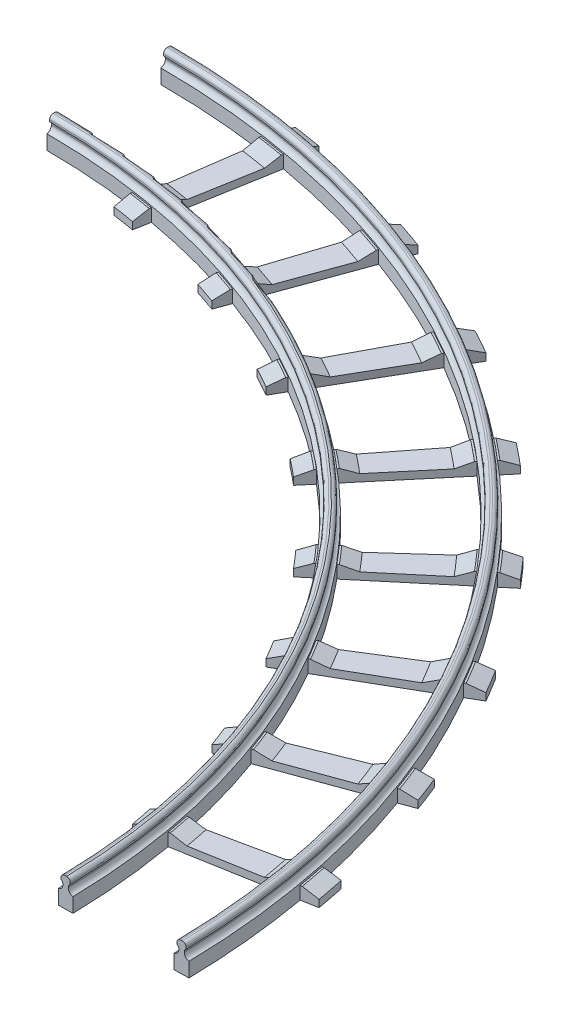
SolidWorks part; units mm, degrees
note: The reader was unsure of these and kept them because the rebuilt part matched: shared geometry of "草图1<7>", "草图2<3>", "草图5<2>".
other "标注1"
sketch "草图3" plane through (-22.25, 4, -10) normal (-0.231, 0.6469, -0.7268) x (-0.9696, -0.2151, 0.1167)
other "标注2"
sketch "草图4" plane through (22.25, 8, -30) normal (0.0083, 0.0567, -0.9984) x (-0.9991, 0.0415, -0.0059)
ref_plane "前视基准面" through (0, 0, 0) normal (0, 0, 1) x (1, 0, 0)
ref_plane "上视基准面" through (0, 0, 0) normal (0, 1, 0) x (1, 0, 0)
ref_plane "右视基准面" through (0, 0, 0) normal (1, 0, 0) x (0, 0, -1)
other "Configuration Table"
sketch "草图1" plane through (0, 0, 0) normal (0, 1, 0) x (1, 0, 0)
  line L0 (-13.75, 14.5) -> (-13.75, -14.5)
  line L13 (-17.75, -14.5) -> (17.75, -14.5)
  line L21 (-17.75, -14.5) -> (-17.75, 14.5)
  line L22 (-17.75, 14.5) -> (17.75, 14.5)
  line L23 (17.75, -14.5) -> (17.75, 14.5)
  line L24 (-17.75, -14.5) -> (17.75, 14.5) construction
  line L25 (-17.75, 14.5) -> (17.75, -14.5) construction
  line L27 (13.75, 14.5) -> (13.75, -14.5)
  line L29 (-13.75, 0) -> (13.75, 0) construction
  line L32 (-22.25, 14.5) -> (22.25, 14.5)
  line L33 (-22.25, 14.5) -> (-22.25, 6.5)
  line L34 (-22.25, 6.5) -> (22.25, 6.5)
  line L35 (22.25, 14.5) -> (22.25, 6.5)
  point P0 (0, 0)
  point P15 (0, 6.5)
  dimension "D3" = 27.5
  dimension "D4" = 8
  dimension "D1" = 35.5
  dimension "D2" = 29
  dimension "D5" = 44.5
extrude "凸台-拉伸1" add sketch "草图1" along normal blind 4 contours L34 L21 L13 L0 | L34 L27 L13 L23 | L27 L34 L23 L22 | L21 L34 L0 L22
extrude "凸台-拉伸2" add sketch "草图1<7>" along normal blind 3.5 contours L34 L35 L32 L33
sketch "草图1<7>" plane through (0, 0, 0) normal (0, 1, 0) x (1, 0, 0) same geometry as "草图1"
sketch "草图2" plane through (0, 0, -14.5) normal (0, 0, -1) x (-1, 0, 0)
  line L0 (18.25, 3.5) -> (22.25, 2)
  line L1 (22.25, 3.5) -> (18.25, 3.5)
  line L2 (22.25, 3.5) -> (22.25, 2)
  line L3 (22.25, 2) -> (18.25, 2) construction
  line L4 (18.25, 3.5) -> (18.25, 2) construction
  line L5 (-22.25, 2) -> (-18.25, 3.5)
  line L6 (-22.25, 3.5) -> (-18.25, 3.5)
  line L7 (-22.25, 3.5) -> (-22.25, 2)
  line L8 (-22.25, 2) -> (-18.25, 2) construction
  line L9 (-18.25, 3.5) -> (-18.25, 2) construction
  line L10 (13.75, 3.5) -> (-13.75, 3.5) construction
  line L11 (-13.25, 3.5) -> (-9.25, 3.5)
  line L12 (-13.25, 3.5) -> (-13.25, 2) construction
  line L13 (-13.25, 2) -> (-9.25, 2) construction
  line L14 (-9.25, 3.5) -> (-9.25, 2)
  line L15 (-13.75, 3.5) -> (-13.25, 3.5) construction
  line L16 (13.25, 3.5) -> (9.25, 3.5)
  line L17 (13.25, 3.5) -> (13.25, 2) construction
  line L18 (13.25, 2) -> (9.25, 2) construction
  line L19 (9.25, 3.5) -> (9.25, 2)
  line L20 (13.25, 3.5) -> (13.75, 3.5) construction
  line L21 (17.75, 3.5) -> (18.25, 3.5) construction
  line L22 (-13.25, 3.5) -> (-9.25, 2)
  line L23 (9.25, 2) -> (13.25, 3.5)
  line L24 (-9.25, 2) -> (9.25, 2)
  line L25 (-9.25, 3.5) -> (9.25, 3.5)
  line L26 (-15.75, 4) -> (-15.75, 6.5) construction
  line L27 (14.5, 8) -> (17, 8)
  line L28 (14.5, 8) -> (14.5, 6.5)
  line L29 (14.5, 6.5) -> (17, 6.5)
  line L30 (17, 8) -> (17, 6.5)
  line L31 (-17, 8) -> (-14.5, 8)
  line L32 (-17, 8) -> (-17, 6.5)
  line L33 (-17, 6.5) -> (-14.5, 6.5)
  line L34 (-14.5, 8) -> (-14.5, 6.5)
  line L35 (-13.75, 4) -> (-17.75, 4) construction
  line L36 (15.75, 6.5) -> (15.75, 4) construction
  line L37 (17.75, 4) -> (13.75, 4) construction
  line L38 (15, 6.5) -> (15, 4)
  line L39 (16.5, 6.5) -> (16.5, 4)
  line L40 (16.5, 4) -> (15.75, 4)
  line L41 (15.75, 4) -> (15, 4)
  line L42 (-16.5, 6.5) -> (-16.5, 4)
  line L43 (-16.5, 4) -> (-15.75, 4)
  line L44 (-15.75, 4) -> (-15, 4)
  line L45 (-15, 4) -> (-15, 6.5)
  line M9 (22.25, 3.5) -> (17.75, 3.5)
  line M11 (17.75, 4) -> (13.75, 4)
  line M13 (13.75, 3.5) -> (-13.75, 3.5)
  line M15 (-13.75, 4) -> (-17.75, 4)
  line M17 (-17.75, 3.5) -> (-22.25, 3.5)
  line M18 (-22.25, 3.5) -> (-22.25, 0)
  line M20 (22.25, 0) -> (22.25, 3.5)
  dimension "D1" = 4
  dimension "D2" = 1.5
  dimension "D3" = 2.5
  dimension "D4" = 1.5
  dimension "D5" = 2.5
  dimension "D6" = 1.5
extrude "切除-拉伸1" cut sketch "草图2" against normal through all contours L14 L24 L19 M13 | L19 L23 M13 | L22 L14 M13 | L5 M18 M17 | L0 M9 M20
extrude "凸台-拉伸4" add sketch "草图2<3>" against normal through all contours L34 L31 L32 L33 | L45 L33 L42 M15 | L30 L27 L28 L29 | L39 L29 L38 M11
sketch "草图2<3>" plane through (0, 0, -14.5) normal (0, 0, -1) x (-1, 0, 0) same geometry as "草图2"
fillet "圆角1" radius 1 4 edges at (-16.5, 6.5, 0) (-15, 6.5, 0) (15, 6.5, 0) (16.5, 6.5, 0)
fillet "圆角2" radius 1.5 4 edges at (16.5, 4, 0) (15, 4, 0) (-15, 4, 0) (-16.5, 4, 0)
fillet "圆角3" radius 1 4 edges at (-17, 8, 0) (14.5, 8, 0) (17, 8, 0) (-14.5, 8, 0)
sketch "草图5" plane through (0, 0, -14.5) normal (0, 0, -1) x (-1, 0, 0)
  line L26 (17, 6.5) -> (17, 7)
  line L27 (16, 8) -> (15.5, 8)
  line L28 (14.5, 7) -> (14.5, 6.5)
  line L29 (15, 5.634) -> (15, 5.479)
  line L30 (13.75, 4) -> (13.75, 3.5)
  line L31 (13.75, 3.5) -> (13.25, 3.5)
  line L32 (13.25, 3.5) -> (9.25, 2)
  line L33 (9.25, 2) -> (-9.25, 2)
  line L34 (-9.25, 2) -> (-13.25, 3.5)
  line L35 (-13.25, 3.5) -> (-13.75, 3.5)
  line L36 (-13.75, 3.5) -> (-13.75, 4)
  line L37 (-15, 5.479) -> (-15, 5.634)
  line L38 (-14.5, 6.5) -> (-14.5, 7)
  line L39 (-15.5, 8) -> (-16, 8)
  line L40 (-17, 7) -> (-17, 6.5)
  line L41 (-16.5, 5.634) -> (-16.5, 5.479)
  line L42 (-17.75, 4) -> (-17.75, 3.5)
  line L43 (-17.75, 3.5) -> (-18.25, 3.5)
  line L44 (-18.25, 3.5) -> (-22.25, 2)
  line L45 (-22.25, 2) -> (-22.25, 0)
  line L46 (-22.25, 0) -> (22.25, 0)
  line L47 (22.25, 0) -> (22.25, 2)
  line L48 (22.25, 2) -> (18.25, 3.5)
  line L49 (18.25, 3.5) -> (17.75, 3.5)
  line L50 (17.75, 3.5) -> (17.75, 4)
  line L51 (16.5, 5.479) -> (16.5, 5.634)
  line L52 (17, 6.5) -> (17, 7)
  line L53 (16, 8) -> (15.5, 8)
  line L54 (14.5, 7) -> (14.5, 6.5)
  line L55 (15, 5.634) -> (15, 5.479)
  line L56 (13.75, 4) -> (13.75, 3.5)
  line L57 (13.75, 3.5) -> (13.25, 3.5)
  line L58 (13.25, 3.5) -> (9.25, 2)
  line L59 (9.25, 2) -> (-9.25, 2)
  line L60 (-9.25, 2) -> (-13.25, 3.5)
  line L61 (-13.25, 3.5) -> (-13.75, 3.5)
  line L62 (-13.75, 3.5) -> (-13.75, 4)
  line L63 (-15, 5.479) -> (-15, 5.634)
  line L64 (-14.5, 6.5) -> (-14.5, 7)
  line L65 (-15.5, 8) -> (-16, 8)
  line L66 (-17, 7) -> (-17, 6.5)
  line L67 (-16.5, 5.634) -> (-16.5, 5.479)
  line L68 (-17.75, 4) -> (-17.75, 3.5)
  line L69 (-17.75, 3.5) -> (-18.25, 3.5)
  line L70 (-18.25, 3.5) -> (-22.25, 2)
  line L71 (-22.25, 2) -> (-22.25, 0)
  line L72 (-22.25, 0) -> (22.25, 0)
  line L73 (22.25, 0) -> (22.25, 2)
  line L74 (22.25, 2) -> (18.25, 3.5)
  line L75 (18.25, 3.5) -> (17.75, 3.5)
  line L76 (17.75, 3.5) -> (17.75, 4)
  line L77 (16.5, 5.479) -> (16.5, 5.634)
  arc A12 (17, 7) -> (16, 8) centre (16, 7) ccw
  arc A13 (15.5, 8) -> (14.5, 7) centre (15.5, 7) ccw
  arc A14 (15, 5.634) -> (14.5, 6.5) centre (14, 5.634) ccw
  arc A15 (13.75, 4) -> (15, 5.479) centre (13.5, 5.479) ccw
  arc A16 (-15, 5.479) -> (-13.75, 4) centre (-13.5, 5.479) ccw
  arc A17 (-14.5, 6.5) -> (-15, 5.634) centre (-14, 5.634) ccw
  arc A18 (-14.5, 7) -> (-15.5, 8) centre (-15.5, 7) ccw
  arc A19 (-16, 8) -> (-17, 7) centre (-16, 7) ccw
  arc A20 (-16.5, 5.634) -> (-17, 6.5) centre (-17.5, 5.634) ccw
  arc A21 (-17.75, 4) -> (-16.5, 5.479) centre (-18, 5.479) ccw
  arc A22 (16.5, 5.479) -> (17.75, 4) centre (18, 5.479) ccw
  arc A23 (17, 6.5) -> (16.5, 5.634) centre (17.5, 5.634) ccw
  arc A24 (17, 7) -> (16, 8) centre (16, 7) ccw
  arc A25 (15.5, 8) -> (14.5, 7) centre (15.5, 7) ccw
  arc A26 (15, 5.634) -> (14.5, 6.5) centre (14, 5.634) ccw
  arc A27 (13.75, 4) -> (15, 5.479) centre (13.5, 5.479) ccw
  arc A28 (-15, 5.479) -> (-13.75, 4) centre (-13.5, 5.479) ccw
  arc A29 (-14.5, 6.5) -> (-15, 5.634) centre (-14, 5.634) ccw
  arc A30 (-14.5, 7) -> (-15.5, 8) centre (-15.5, 7) ccw
  arc A31 (-16, 8) -> (-17, 7) centre (-16, 7) ccw
  arc A32 (-16.5, 5.634) -> (-17, 6.5) centre (-17.5, 5.634) ccw
  arc A33 (-17.75, 4) -> (-16.5, 5.479) centre (-18, 5.479) ccw
  arc A34 (16.5, 5.479) -> (17.75, 4) centre (18, 5.479) ccw
  arc A35 (17, 6.5) -> (16.5, 5.634) centre (17.5, 5.634) ccw
  dimension "D1" = 0
sketch "草图7" plane through (0, 0, -14.5) normal (0, 0, -1) x (-1, 0, 0)
  line L0 (-17.75, 3.5) -> (-17.75, 0)
  line L1 (-13.75, 3.5) -> (-13.75, 0)
  line L2 (13.75, 3.5) -> (13.75, 0)
  line L3 (17.75, 3.5) -> (17.75, 0)
  line L4 (13.75, 0) -> (17.75, 0)
  line L26 (17, 6.5) -> (17, 7)
  line L27 (16, 8) -> (15.5, 8)
  line L28 (14.5, 7) -> (14.5, 6.5)
  line L29 (15, 5.634) -> (15, 5.479)
  line L30 (13.75, 4) -> (13.75, 3.5)
  line L31 (13.75, 3.5) -> (13.25, 3.5)
  line L32 (13.25, 3.5) -> (9.25, 2)
  line L33 (9.25, 2) -> (-9.25, 2)
  line L34 (-9.25, 2) -> (-13.25, 3.5)
  line L35 (-13.25, 3.5) -> (-13.75, 3.5)
  line L36 (-13.75, 3.5) -> (-13.75, 4)
  line L37 (-15, 5.479) -> (-15, 5.634)
  line L38 (-14.5, 6.5) -> (-14.5, 7)
  line L39 (-15.5, 8) -> (-16, 8)
  line L40 (-17, 7) -> (-17, 6.5)
  line L41 (-16.5, 5.634) -> (-16.5, 5.479)
  line L42 (-17.75, 4) -> (-17.75, 3.5)
  line L43 (-17.75, 3.5) -> (-18.25, 3.5)
  line L44 (-18.25, 3.5) -> (-22.25, 2)
  line L45 (-22.25, 2) -> (-22.25, 0)
  line L46 (-22.25, 0) -> (22.25, 0)
  line L47 (22.25, 0) -> (22.25, 2)
  line L48 (22.25, 2) -> (18.25, 3.5)
  line L49 (18.25, 3.5) -> (17.75, 3.5)
  line L50 (17.75, 3.5) -> (17.75, 4)
  line L51 (16.5, 5.479) -> (16.5, 5.634)
  line L52 (17, 6.5) -> (17, 7)
  line L53 (16, 8) -> (15.5, 8)
  line L54 (14.5, 7) -> (14.5, 6.5)
  line L55 (15, 5.634) -> (15, 5.479)
  line L56 (13.75, 4) -> (13.75, 3.5)
  line L62 (-13.75, 3.5) -> (-13.75, 4)
  line L63 (-15, 5.479) -> (-15, 5.634)
  line L64 (-14.5, 6.5) -> (-14.5, 7)
  line L65 (-15.5, 8) -> (-16, 8)
  line L66 (-17, 7) -> (-17, 6.5)
  line L67 (-16.5, 5.634) -> (-16.5, 5.479)
  line L68 (-17.75, 4) -> (-17.75, 3.5)
  line L72 (-17.75, 0) -> (-13.75, 0)
  line L76 (17.75, 3.5) -> (17.75, 4)
  line L77 (16.5, 5.479) -> (16.5, 5.634)
  arc A12 (17, 7) -> (16, 8) centre (16, 7) ccw
  arc A13 (15.5, 8) -> (14.5, 7) centre (15.5, 7) ccw
  arc A14 (15, 5.634) -> (14.5, 6.5) centre (14, 5.634) ccw
  arc A15 (13.75, 4) -> (15, 5.479) centre (13.5, 5.479) ccw
  arc A16 (-15, 5.479) -> (-13.75, 4) centre (-13.5, 5.479) ccw
  arc A17 (-14.5, 6.5) -> (-15, 5.634) centre (-14, 5.634) ccw
  arc A18 (-14.5, 7) -> (-15.5, 8) centre (-15.5, 7) ccw
  arc A19 (-16, 8) -> (-17, 7) centre (-16, 7) ccw
  arc A20 (-16.5, 5.634) -> (-17, 6.5) centre (-17.5, 5.634) ccw
  arc A21 (-17.75, 4) -> (-16.5, 5.479) centre (-18, 5.479) ccw
  arc A22 (16.5, 5.479) -> (17.75, 4) centre (18, 5.479) ccw
  arc A23 (17, 6.5) -> (16.5, 5.634) centre (17.5, 5.634) ccw
  arc A24 (17, 7) -> (16, 8) centre (16, 7) ccw
  arc A25 (15.5, 8) -> (14.5, 7) centre (15.5, 7) ccw
  arc A26 (15, 5.634) -> (14.5, 6.5) centre (14, 5.634) ccw
  arc A27 (13.75, 4) -> (15, 5.479) centre (13.5, 5.479) ccw
  arc A28 (-15, 5.479) -> (-13.75, 4) centre (-13.5, 5.479) ccw
  arc A29 (-14.5, 6.5) -> (-15, 5.634) centre (-14, 5.634) ccw
  arc A30 (-14.5, 7) -> (-15.5, 8) centre (-15.5, 7) ccw
  arc A31 (-16, 8) -> (-17, 7) centre (-16, 7) ccw
  arc A32 (-16.5, 5.634) -> (-17, 6.5) centre (-17.5, 5.634) ccw
  arc A33 (-17.75, 4) -> (-16.5, 5.479) centre (-18, 5.479) ccw
  arc A34 (16.5, 5.479) -> (17.75, 4) centre (18, 5.479) ccw
  arc A35 (17, 6.5) -> (16.5, 5.634) centre (17.5, 5.634) ccw
  dimension "D1" = 0
sketch "草图6" plane through (0, 0, -14.5) normal (0, 0, -1) x (-1, 0, 0)
  line L0 (0, 0) -> (200, 0) construction
  line L1 (200, 10) -> (200, -10)
  dimension "D1" = 200
  dimension "D2" = 20
revolve "旋转2" add sketch "草图7" angle 92 about L1
extrude "切除-拉伸5" cut sketch "草图5<2>" against normal through all
sketch "草图5<2>" plane through (0, 0, -14.5) normal (0, 0, -1) x (-1, 0, 0) same geometry as "草图5"
revolve "旋转1" add sketch "草图5" angle 2 about L1
pattern_circular "阵列(圆周)1" count 10 every 10 about axis through (-200, 0, -14.5) along (0, 1, 0) of "旋转1"
sketch "草图8" plane through (0, 0, -14.5) normal (0, 0, 1) x (1, 0, 0)
  line L78 (-22.25, 2) -> (-22.25, 0)
  line L79 (-22.25, 0) -> (22.25, 0)
  line L80 (22.25, 0) -> (22.25, 2)
  line L81 (22.25, 2) -> (18.25, 3.5)
  line L82 (18.25, 3.5) -> (17.75, 3.5)
  line L83 (17.75, 3.5) -> (17.75, 4)
  line L84 (16.5, 5.479) -> (16.5, 5.634)
  line L85 (17, 6.5) -> (17, 7)
  line L86 (16, 8) -> (15.5, 8)
  line L87 (14.5, 7) -> (14.5, 6.5)
  line L88 (15, 5.634) -> (15, 5.479)
  line L89 (13.75, 4) -> (13.75, 3.5)
  line L90 (13.75, 3.5) -> (13.25, 3.5)
  line L91 (13.25, 3.5) -> (9.25, 2)
  line L92 (9.25, 2) -> (-9.25, 2)
  line L93 (-9.25, 2) -> (-13.25, 3.5)
  line L94 (-13.25, 3.5) -> (-13.75, 3.5)
  line L95 (-13.75, 3.5) -> (-13.75, 4)
  line L96 (-15, 5.479) -> (-15, 5.634)
  line L97 (-14.5, 6.5) -> (-14.5, 7)
  line L98 (-15.5, 8) -> (-16, 8)
  line L99 (-17, 7) -> (-17, 6.5)
  line L100 (-16.5, 5.634) -> (-16.5, 5.479)
  line L101 (-17.75, 4) -> (-17.75, 3.5)
  line L102 (-17.75, 3.5) -> (-18.25, 3.5)
  line L103 (-18.25, 3.5) -> (-22.25, 2)
  line L104 (-22.25, 2) -> (-22.25, 0)
  line L105 (-22.25, 0) -> (22.25, 0)
  line L106 (22.25, 0) -> (22.25, 2)
  line L107 (22.25, 2) -> (18.25, 3.5)
  line L108 (18.25, 3.5) -> (17.75, 3.5)
  line L109 (17.75, 3.5) -> (17.75, 4)
  line L110 (16.5, 5.479) -> (16.5, 5.634)
  line L111 (17, 6.5) -> (17, 7)
  line L112 (16, 8) -> (15.5, 8)
  line L113 (14.5, 7) -> (14.5, 6.5)
  line L114 (15, 5.634) -> (15, 5.479)
  line L115 (13.75, 4) -> (13.75, 3.5)
  line L116 (13.75, 3.5) -> (13.25, 3.5)
  line L117 (13.25, 3.5) -> (9.25, 2)
  line L118 (9.25, 2) -> (-9.25, 2)
  line L119 (-9.25, 2) -> (-13.25, 3.5)
  line L120 (-13.25, 3.5) -> (-13.75, 3.5)
  line L121 (-13.75, 3.5) -> (-13.75, 4)
  line L122 (-15, 5.479) -> (-15, 5.634)
  line L123 (-14.5, 6.5) -> (-14.5, 7)
  line L124 (-15.5, 8) -> (-16, 8)
  line L125 (-17, 7) -> (-17, 6.5)
  line L126 (-16.5, 5.634) -> (-16.5, 5.479)
  line L127 (-17.75, 4) -> (-17.75, 3.5)
  line L128 (-17.75, 3.5) -> (-18.25, 3.5)
  line L129 (-18.25, 3.5) -> (-22.25, 2)
  arc A36 (16.5, 5.479) -> (17.75, 4) centre (18, 5.479) ccw
  arc A37 (17, 6.5) -> (16.5, 5.634) centre (17.5, 5.634) ccw
  arc A38 (17, 7) -> (16, 8) centre (16, 7) ccw
  arc A39 (15.5, 8) -> (14.5, 7) centre (15.5, 7) ccw
  arc A40 (15, 5.634) -> (14.5, 6.5) centre (14, 5.634) ccw
  arc A41 (13.75, 4) -> (15, 5.479) centre (13.5, 5.479) ccw
  arc A42 (-15, 5.479) -> (-13.75, 4) centre (-13.5, 5.479) ccw
  arc A43 (-14.5, 6.5) -> (-15, 5.634) centre (-14, 5.634) ccw
  arc A44 (-14.5, 7) -> (-15.5, 8) centre (-15.5, 7) ccw
  arc A45 (-16, 8) -> (-17, 7) centre (-16, 7) ccw
  arc A46 (-16.5, 5.634) -> (-17, 6.5) centre (-17.5, 5.634) ccw
  arc A47 (-17.75, 4) -> (-16.5, 5.479) centre (-18, 5.479) ccw
  arc A48 (16.5, 5.479) -> (17.75, 4) centre (18, 5.479) ccw
  arc A49 (17, 6.5) -> (16.5, 5.634) centre (17.5, 5.634) ccw
  arc A50 (17, 7) -> (16, 8) centre (16, 7) ccw
  arc A51 (15.5, 8) -> (14.5, 7) centre (15.5, 7) ccw
  arc A52 (15, 5.634) -> (14.5, 6.5) centre (14, 5.634) ccw
  arc A53 (13.75, 4) -> (15, 5.479) centre (13.5, 5.479) ccw
  arc A54 (-15, 5.479) -> (-13.75, 4) centre (-13.5, 5.479) ccw
  arc A55 (-14.5, 6.5) -> (-15, 5.634) centre (-14, 5.634) ccw
  arc A56 (-14.5, 7) -> (-15.5, 8) centre (-15.5, 7) ccw
  arc A57 (-16, 8) -> (-17, 7) centre (-16, 7) ccw
  arc A58 (-16.5, 5.634) -> (-17, 6.5) centre (-17.5, 5.634) ccw
  arc A59 (-17.75, 4) -> (-16.5, 5.479) centre (-18, 5.479) ccw
  dimension "D1" = 0
revolve "切除-旋转1" cut sketch "草图8" angle 1 about L1
sketch "草图9" plane through (-199.2507, 0, 6.958) normal (-0.9994, 0, 0.0349) x (0.0349, 0, 0.9994)
  line L8 (-243.7211, 0) -> (-199.2211, 0)
  line L16 (-243.7211, 0) -> (-199.2211, 0)
  line L24 (-203.7211, 3.5) -> (-203.7211, 4)
  line L26 (-203.7211, 3.5) -> (-203.7211, 4)
  line L28 (-204.9711, 5.479) -> (-204.9711, 5.634)
  line L30 (-204.9711, 5.479) -> (-204.9711, 5.634)
  line L32 (-204.4711, 6.5) -> (-204.4711, 7)
  line L34 (-204.4711, 6.5) -> (-204.4711, 7)
  line L94 (-205.4711, 8) -> (-205.9711, 8)
  line L98 (-205.4711, 8) -> (-205.9711, 8)
  line L102 (-206.9711, 7) -> (-206.9711, 6.5)
  line L106 (-206.9711, 7) -> (-206.9711, 6.5)
  line L110 (-206.4711, 5.634) -> (-206.4711, 5.479)
  line L113 (-206.4711, 5.634) -> (-206.4711, 5.479)
  line L115 (-207.7211, 4) -> (-207.7211, 3.5)
  line L117 (-207.7211, 4) -> (-207.7211, 3.5)
  line L119 (-235.2211, 3.5) -> (-235.2211, 4)
  line L121 (-235.2211, 3.5) -> (-235.2211, 4)
  line L123 (-236.4711, 5.479) -> (-236.4711, 5.634)
  line L124 (-236.4711, 5.479) -> (-236.4711, 5.634)
  line L125 (-235.9711, 6.5) -> (-235.9711, 7)
  line L126 (-235.9711, 6.5) -> (-235.9711, 7)
  line L127 (-236.9711, 8) -> (-237.4711, 8)
  line L128 (-236.9711, 8) -> (-237.4711, 8)
  line L129 (-238.4711, 7) -> (-238.4711, 6.5)
  line L130 (-238.4711, 7) -> (-238.4711, 6.5)
  line L131 (-237.9711, 5.634) -> (-237.9711, 5.479)
  line L132 (-237.9711, 5.634) -> (-237.9711, 5.479)
  line L133 (-239.2211, 4) -> (-239.2211, 3.5)
  line L134 (-239.2211, 4) -> (-239.2211, 3.5)
  line L135 (-199.2211, 0) -> (-199.2211, 2)
  line L136 (-199.2211, 0) -> (-199.2211, 2)
  line L137 (-199.2211, 2) -> (-203.2211, 3.5)
  line L138 (-199.2211, 2) -> (-203.2211, 3.5)
  line L139 (-203.2211, 3.5) -> (-203.7211, 3.5)
  line L140 (-203.2211, 3.5) -> (-203.7211, 3.5)
  line L141 (-207.7211, 3.5) -> (-208.2211, 3.5)
  line L142 (-207.7211, 3.5) -> (-208.2211, 3.5)
  line L143 (-208.2211, 3.5) -> (-212.2211, 2)
  line L144 (-208.2211, 3.5) -> (-212.2211, 2)
  line L145 (-212.2211, 2) -> (-230.7211, 2)
  line L146 (-212.2211, 2) -> (-230.7211, 2)
  line L147 (-230.7211, 2) -> (-234.7211, 3.5)
  line L148 (-230.7211, 2) -> (-234.7211, 3.5)
  line L149 (-234.7211, 3.5) -> (-235.2211, 3.5)
  line L150 (-234.7211, 3.5) -> (-235.2211, 3.5)
  line L151 (-239.2211, 3.5) -> (-239.7211, 3.5)
  line L152 (-239.2211, 3.5) -> (-239.7211, 3.5)
  line L153 (-239.7211, 3.5) -> (-243.7211, 2)
  line L154 (-239.7211, 3.5) -> (-243.7211, 2)
  line L155 (-243.7211, 2) -> (-243.7211, 0)
  line L156 (-243.7211, 2) -> (-243.7211, 0)
  arc A6 (-204.9711, 5.479) -> (-203.7211, 4) centre (-203.4711, 5.479) ccw
  arc A14 (-204.9711, 5.479) -> (-203.7211, 4) centre (-203.4711, 5.479) ccw
  arc A19 (-204.4711, 6.5) -> (-204.9711, 5.634) centre (-203.9711, 5.634) ccw
  arc A21 (-204.4711, 6.5) -> (-204.9711, 5.634) centre (-203.9711, 5.634) ccw
  arc A23 (-204.4711, 7) -> (-205.4711, 8) centre (-205.4711, 7) ccw
  arc A38 (-204.4711, 7) -> (-205.4711, 8) centre (-205.4711, 7) ccw
  arc A54 (-205.9711, 8) -> (-206.9711, 7) centre (-205.9711, 7) ccw
  arc A55 (-205.9711, 8) -> (-206.9711, 7) centre (-205.9711, 7) ccw
  arc A56 (-206.4711, 5.634) -> (-206.9711, 6.5) centre (-207.4711, 5.634) ccw
  arc A57 (-206.4711, 5.634) -> (-206.9711, 6.5) centre (-207.4711, 5.634) ccw
  arc A58 (-207.7211, 4) -> (-206.4711, 5.479) centre (-207.9711, 5.479) ccw
  arc A59 (-207.7211, 4) -> (-206.4711, 5.479) centre (-207.9711, 5.479) ccw
  arc A60 (-236.4711, 5.479) -> (-235.2211, 4) centre (-234.9711, 5.479) ccw
  arc A61 (-236.4711, 5.479) -> (-235.2211, 4) centre (-234.9711, 5.479) ccw
  arc A62 (-235.9711, 6.5) -> (-236.4711, 5.634) centre (-235.4711, 5.634) ccw
  arc A63 (-235.9711, 6.5) -> (-236.4711, 5.634) centre (-235.4711, 5.634) ccw
  arc A64 (-235.9711, 7) -> (-236.9711, 8) centre (-236.9711, 7) ccw
  arc A65 (-235.9711, 7) -> (-236.9711, 8) centre (-236.9711, 7) ccw
  arc A66 (-237.4711, 8) -> (-238.4711, 7) centre (-237.4711, 7) ccw
  arc A67 (-237.4711, 8) -> (-238.4711, 7) centre (-237.4711, 7) ccw
  arc A68 (-237.9711, 5.634) -> (-238.4711, 6.5) centre (-238.9711, 5.634) ccw
  arc A69 (-237.9711, 5.634) -> (-238.4711, 6.5) centre (-238.9711, 5.634) ccw
  arc A70 (-239.2211, 4) -> (-237.9711, 5.479) centre (-239.4711, 5.479) ccw
  arc A71 (-239.2211, 4) -> (-237.9711, 5.479) centre (-239.4711, 5.479) ccw
  dimension "D1" = 0
revolve "切除-旋转2" cut sketch "草图9" angle 1 about L1
sketch "草图10" plane through (-0.3139, 0, -17.9855) normal (0.0175, 0, 0.9998) x (0.9998, 0, -0.0175)
  line L0 (-17.4665, 3.5) -> (-17.4665, 0)
  line L1 (-13.4665, 3.5) -> (-13.4665, 0)
  line L2 (14.0335, 3.5) -> (14.0335, 0)
  line L3 (18.0335, 3.5) -> (18.0335, 0)
  line L4 (-13.4665, 0) -> (14.0335, 0)
  line L5 (18.0335, 0) -> (22.5335, 0)
  line L26 (-17.9665, 3.5) -> (-21.9665, 2)
  line L27 (-21.9665, 2) -> (-21.9665, 0)
  line L28 (-21.9665, 0) -> (22.5335, 0)
  line L29 (22.5335, 0) -> (22.5335, 2)
  line L30 (22.5335, 2) -> (18.5335, 3.5)
  line L31 (18.5335, 3.5) -> (18.0335, 3.5)
  line L32 (18.0335, 3.5) -> (18.0335, 4)
  line L33 (16.7835, 5.479) -> (16.7835, 5.634)
  line L34 (17.2835, 6.5) -> (17.2835, 7)
  line L35 (16.2835, 8) -> (15.7835, 8)
  line L36 (14.7835, 7) -> (14.7835, 6.5)
  line L37 (15.2835, 5.634) -> (15.2835, 5.479)
  line L38 (14.0335, 4) -> (14.0335, 3.5)
  line L39 (14.0335, 3.5) -> (13.5335, 3.5)
  line L40 (13.5335, 3.5) -> (9.5335, 2)
  line L41 (9.5335, 2) -> (-8.9665, 2)
  line L42 (-8.9665, 2) -> (-12.9665, 3.5)
  line L43 (-12.9665, 3.5) -> (-13.4665, 3.5)
  line L44 (-13.4665, 3.5) -> (-13.4665, 4)
  line L45 (-14.7165, 5.479) -> (-14.7165, 5.634)
  line L46 (-14.2165, 6.5) -> (-14.2165, 7)
  line L47 (-15.2165, 8) -> (-15.7165, 8)
  line L48 (-16.7165, 7) -> (-16.7165, 6.5)
  line L49 (-16.2165, 5.634) -> (-16.2165, 5.479)
  line L50 (-17.4665, 4) -> (-17.4665, 3.5)
  line L51 (-17.4665, 3.5) -> (-17.9665, 3.5)
  line L52 (-17.9665, 3.5) -> (-21.9665, 2)
  line L53 (-21.9665, 2) -> (-21.9665, 0)
  line L54 (-21.9665, 0) -> (-17.4665, 0)
  line L55 (22.5335, 0) -> (22.5335, 2)
  line L56 (22.5335, 2) -> (18.5335, 3.5)
  line L57 (18.5335, 3.5) -> (18.0335, 3.5)
  line L65 (14.0335, 3.5) -> (13.5335, 3.5)
  line L66 (13.5335, 3.5) -> (9.5335, 2)
  line L67 (9.5335, 2) -> (-8.9665, 2)
  line L68 (-8.9665, 2) -> (-12.9665, 3.5)
  line L69 (-12.9665, 3.5) -> (-13.4665, 3.5)
  line L77 (-17.4665, 3.5) -> (-17.9665, 3.5)
  arc A12 (16.7835, 5.479) -> (18.0335, 4) centre (18.2835, 5.479) ccw
  arc A13 (17.2835, 6.5) -> (16.7835, 5.634) centre (17.7835, 5.634) ccw
  arc A14 (17.2835, 7) -> (16.2835, 8) centre (16.2835, 7) ccw
  arc A15 (15.7835, 8) -> (14.7835, 7) centre (15.7835, 7) ccw
  arc A16 (15.2835, 5.634) -> (14.7835, 6.5) centre (14.2835, 5.634) ccw
  arc A17 (14.0335, 4) -> (15.2835, 5.479) centre (13.7835, 5.479) ccw
  arc A18 (-14.7165, 5.479) -> (-13.4665, 4) centre (-13.2165, 5.479) ccw
  arc A19 (-14.2165, 6.5) -> (-14.7165, 5.634) centre (-13.7165, 5.634) ccw
  arc A20 (-14.2165, 7) -> (-15.2165, 8) centre (-15.2165, 7) ccw
  arc A21 (-15.7165, 8) -> (-16.7165, 7) centre (-15.7165, 7) ccw
  arc A22 (-16.2165, 5.634) -> (-16.7165, 6.5) centre (-17.2165, 5.634) ccw
  arc A23 (-17.4665, 4) -> (-16.2165, 5.479) centre (-17.7165, 5.479) ccw
  dimension "D1" = 0
revolve "切除-旋转3" cut sketch "草图10" angle 1 about L1
sketch "草图11" plane through (-199.6861, 0, 3.4855) normal (-0.9998, 0, 0.0175) x (0.0175, 0, 0.9998)
  line L6 (-169.4701, 3.5) -> (-169.4701, 0)
  line L7 (-240.2383, 0) -> (-195.7383, 0) construction
  line L8 (-169.4701, 0) -> (-240.2383, 0)
  line L9 (-231.7383, 3.5) -> (-231.7383, 0)
  line L10 (-231.7383, 0) -> (-137.9701, 0)
  line L11 (-137.9701, 0) -> (-137.9701, 102.2682)
  line L12 (-133.9701, -102.2682) -> (-133.9701, 0)
  line L13 (-133.9701, 0) -> (-236.2383, 0)
  line L14 (-231.7383, 3.5) -> (-231.7383, 4) construction
revolve "切除-旋转4" cut sketch "草图11" angle 1 about L1
